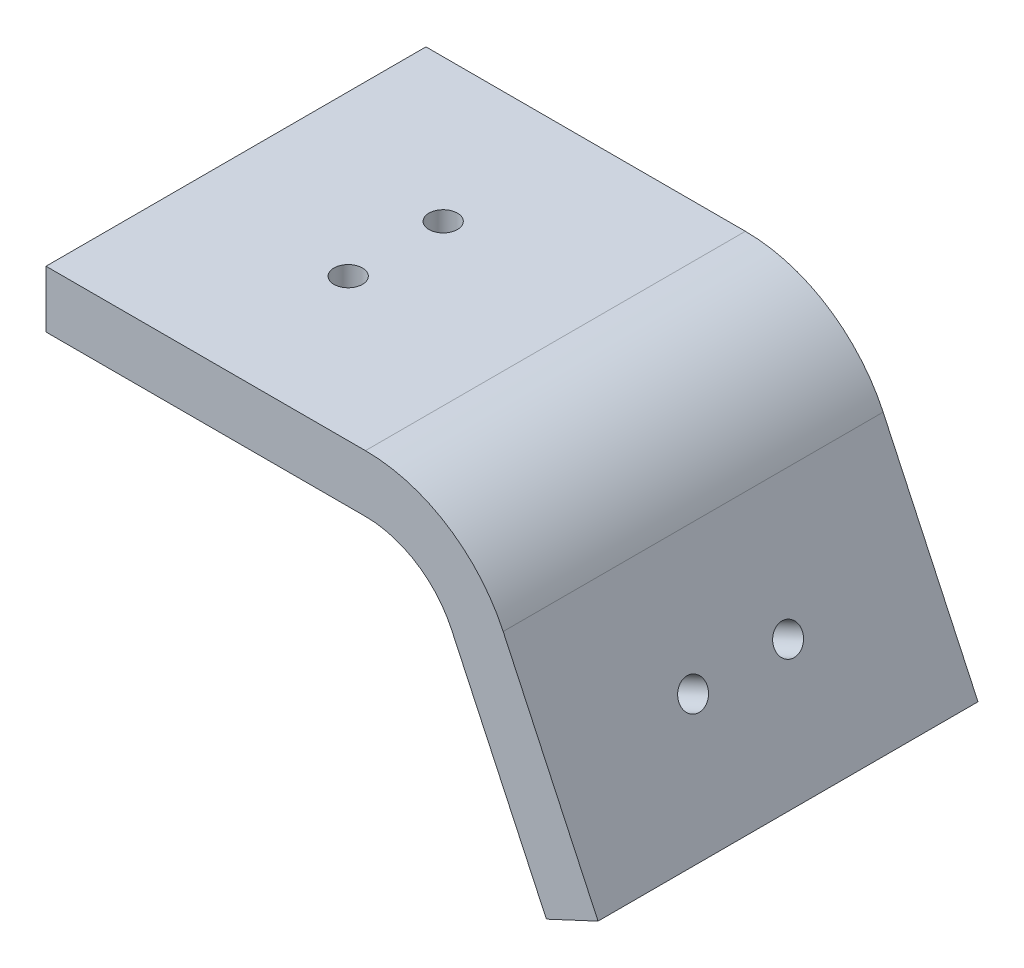
SolidWorks part; units mm, degrees
material "Acrilico TEC"
ref_plane "Front Plane" through (0, 0, 0) normal (0, 0, 1) x (1, 0, 0)
ref_plane "Top Plane" through (0, 0, 0) normal (0, 1, 0) x (1, 0, 0)
ref_plane "Right Plane" through (0, 0, 0) normal (1, 0, 0) x (0, 0, -1)
sketch "Sketch1" plane through (0, 0, 0) normal (0, 0, 1) x (1, 0, 0)
  line L0 (0, 0) -> (-9.9862, 21.4154)
  line L1 (-19.0493, 27.1892) -> (-52.6785, 27.1892)
  line L2 (5.4378, 2.5357) -> (-4.5483, 23.9511)
  line L3 (-19.0493, 33.1892) -> (-52.6785, 33.1892)
  line L4 (-52.6785, 33.1892) -> (-52.6785, 27.1892)
  line L5 (5.4378, 2.5357) -> (0, 0)
  arc A0 (-9.9862, 21.4154) -> (-19.0493, 27.1892) centre (-19.0493, 17.1892) ccw
  arc A1 (-4.5483, 23.9511) -> (-19.0493, 33.1892) centre (-19.0493, 17.1892) ccw
  point P6 (-12.6785, 27.1892)
  dimension "D4" = 10
  dimension "D1" = 115
  dimension "D2" = 30
  dimension "D3" = 40
  dimension "D5" = 6
extrude "Boss-Extrude1" add sketch "Sketch1" along normal blind 40
sketch "Sketch2" plane through (0, 33.1892, 0) normal (0, 1, 0) x (1, 0, 0)
  line L0 (-19.0493, -20) -> (-52.6785, -20) construction
  line L1 (-19.0493, -40) -> (-19.0493, 0) construction
  line L2 (-52.6785, -40) -> (-52.6785, 0) construction
  line L3 (-35.8639, -15) -> (-35.8639, -20)
  circle A0 centre (-35.8639, -15) radius 1.5
  circle A1 centre (-35.8639, -25) radius 1.5
  dimension "D2" = 3
  dimension "D1" = 5
extrude "Cut-Extrude1" cut sketch "Sketch2" against normal blind 40 contours A0 | A1 region at (-34.8332, 33.1892, 16.0307) region at (-35.8639, 33.1892, 25)
sketch "Sketch3" plane through (5.4378, 2.5357, 0) normal (0.9063, 0.4226, 0) x (0, 0, -1)
  line L0 (-20, 23.6293) -> (-20, 0) construction
  line L1 (-40, 23.6293) -> (0, 23.6293) construction
  line L2 (-40, 0) -> (0, 0) construction
  line L3 (-15, 11.8146) -> (-20, 11.8146) construction
  circle A0 centre (-15, 11.8146) radius 1.5
  circle A1 centre (-25, 11.8146) radius 1.5
  dimension "D2" = 3
  dimension "D1" = 5
extrude "Cut-Extrude2" cut sketch "Sketch3" against normal blind 40
